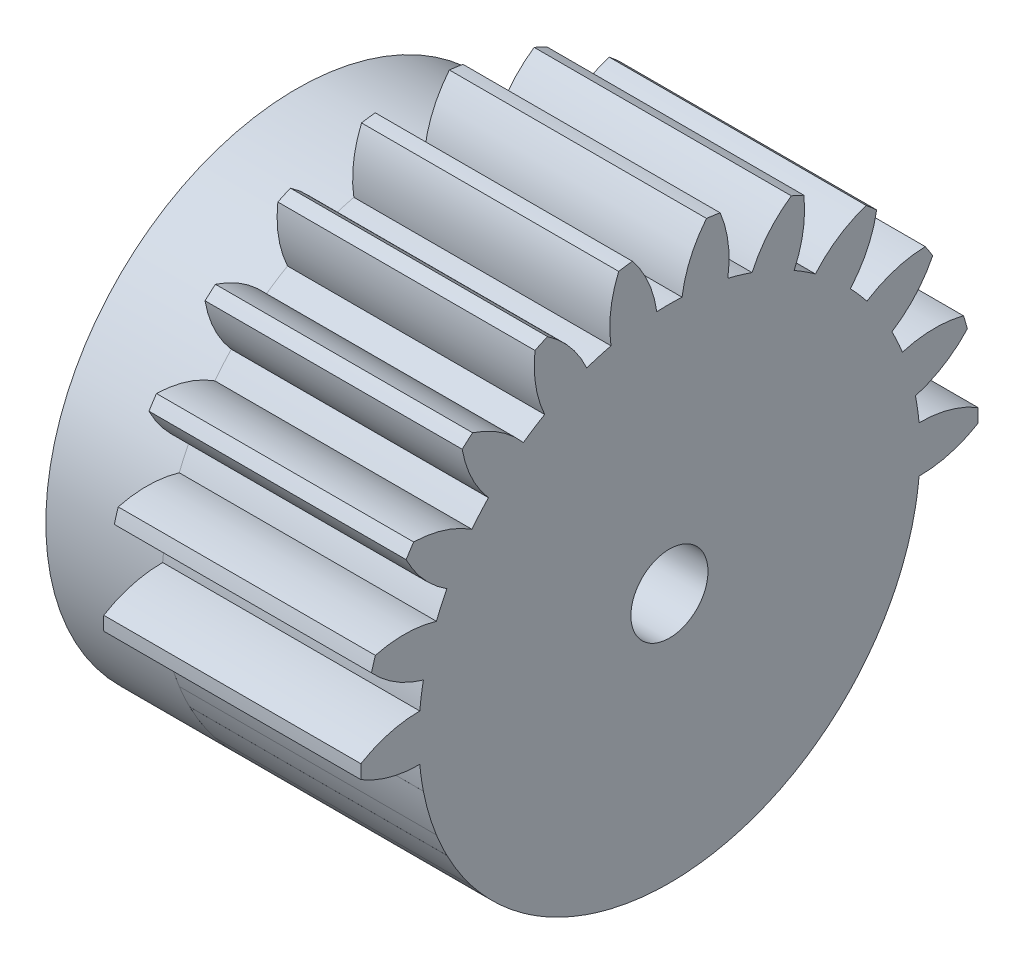
SolidWorks part; units mm, degrees
ref_plane "Front Plane" through (0, 0, 0) normal (0, 0, 1) x (1, 0, 0)
ref_plane "Top Plane" through (0, 0, 0) normal (0, 1, 0) x (1, 0, 0)
ref_plane "Right Plane" through (0, 0, 0) normal (1, 0, 0) x (0, 0, -1)
ref_plane "Plane2" through (4.0389, 0, 0) normal (1, 0, 0) x (0, 0, -1)
sketch "Sketch5" plane through (4.0389, 0, 0) normal (1, 0, 0) x (0, 0, -1)
  circle A0 centre (3.23, 4.4522) radius 1.5
  arc A1 (-8.767, 4.1839) -> (-6.4774, 3.5525) centre (-6.496, 7.9525) ccw
  arc A2 (-6.4774, 3.5525) -> (-6.3377, 2.5805) centre (3.23, 4.4522) ccw
  arc A3 (-6.3377, 2.5805) -> (-8.3567, 1.3296) centre (-5.1159, -1.6464) ccw
  arc A4 (-8.3567, 1.3296) -> (-8.2055, 0.8148) centre (3.23, 4.4522) ccw
  arc A5 (-8.2055, 0.8148) -> (-5.8308, 0.8541) centre (-7.0882, 5.0706) ccw
  arc A6 (-5.8308, 0.8541) -> (-5.4228, -0.0392) centre (3.23, 4.4522) ccw
  arc A7 (-5.4228, -0.0392) -> (-7.0076, -1.8082) centre (-3.0596, -3.7507) ccw
  arc A8 (-7.0076, -1.8082) -> (-6.7175, -2.2596) centre (3.23, 4.4522) ccw
  arc A9 (-6.7175, -2.2596) -> (-4.45, -1.5529) centre (-6.8444, 2.1386) ccw
  arc A10 (-4.45, -1.5529) -> (-3.807, -2.295) centre (3.23, 4.4522) ccw
  arc A11 (-3.807, -2.295) -> (-4.8292, -4.4389) centre (-0.4938, -5.1904) ccw
  arc A12 (-4.8292, -4.4389) -> (-4.4237, -4.7902) centre (3.23, 4.4522) ccw
  arc A13 (-4.4237, -4.7902) -> (-2.4471, -3.4733) centre (-5.7845, -0.606) ccw
  arc A14 (-2.4471, -3.4733) -> (-1.621, -4.0043) centre (3.23, 4.4522) ccw
  arc A15 (-1.621, -4.0043) -> (-1.9978, -6.3492) centre (2.3736, -5.8489) ccw
  arc A16 (-1.9978, -6.3492) -> (-1.5097, -6.5721) centre (3.23, 4.4522) ccw
  arc A17 (-1.5097, -6.5721) -> (0.0157, -4.7517) centre (-3.9943, -2.9408) ccw
  arc A18 (0.0157, -4.7517) -> (0.9579, -5.0284) centre (3.23, 4.4522) ccw
  arc A19 (0.9579, -5.0284) -> (1.257, -7.3845) centre (5.3105, -5.6729) ccw
  arc A20 (1.257, -7.3845) -> (1.7882, -7.4609) centre (3.23, 4.4522) ccw
  arc A21 (1.7882, -7.4609) -> (2.739, -5.2845) centre (-1.6189, -4.6766) ccw
  arc A22 (2.739, -5.2845) -> (3.721, -5.2845) centre (3.23, 4.4522) ccw
  arc A23 (3.721, -5.2845) -> (4.6718, -7.4609) centre (8.0788, -4.6766) ccw
  arc A24 (4.6718, -7.4609) -> (5.2029, -7.3845) centre (3.23, 4.4522) ccw
  arc A25 (5.2029, -7.3845) -> (5.502, -5.0284) centre (1.1494, -5.6729) ccw
  arc A26 (5.502, -5.0284) -> (6.4442, -4.7517) centre (3.23, 4.4522) ccw
  arc A27 (6.4442, -4.7517) -> (7.9696, -6.5721) centre (10.4542, -2.9408) ccw
  arc A28 (7.9696, -6.5721) -> (8.4577, -6.3492) centre (3.23, 4.4522) ccw
  arc A29 (8.4577, -6.3492) -> (8.0809, -4.0043) centre (4.0863, -5.8489) ccw
  arc A30 (8.0809, -4.0043) -> (8.907, -3.4733) centre (3.23, 4.4522) ccw
  arc A31 (8.907, -3.4733) -> (10.8836, -4.7902) centre (12.2444, -0.606) ccw
  arc A32 (10.8836, -4.7902) -> (11.2891, -4.4389) centre (3.23, 4.4522) ccw
  arc A33 (11.2891, -4.4389) -> (10.2669, -2.295) centre (6.9537, -5.1904) ccw
  arc A34 (10.2669, -2.295) -> (10.9099, -1.5529) centre (3.23, 4.4522) ccw
  arc A35 (10.9099, -1.5529) -> (13.1774, -2.2596) centre (13.3043, 2.1386) ccw
  arc A36 (13.1774, -2.2596) -> (13.4675, -1.8082) centre (3.23, 4.4522) ccw
  arc A37 (13.4675, -1.8082) -> (11.8827, -0.0392) centre (9.5195, -3.7507) ccw
  arc A38 (11.8827, -0.0392) -> (12.2907, 0.8541) centre (3.23, 4.4522) ccw
  arc A39 (12.2907, 0.8541) -> (14.6654, 0.8148) centre (13.5481, 5.0706) ccw
  arc A40 (14.6654, 0.8148) -> (14.8166, 1.3296) centre (3.23, 4.4522) ccw
  arc A41 (14.8166, 1.3296) -> (12.7976, 2.5805) centre (11.5758, -1.6464) ccw
  arc A42 (12.7976, 2.5805) -> (12.9374, 3.5525) centre (3.23, 4.4522) ccw
  arc A43 (12.9374, 3.5525) -> (15.227, 4.1839) centre (12.9559, 7.9525) ccw
  arc A44 (15.227, 4.1839) -> (15.227, 4.7205) centre (3.23, 4.4522) ccw
  arc A45 (15.227, 4.7205) -> (12.9374, 5.3518) centre (12.9559, 0.9519) ccw
  arc A46 (12.9374, 5.3518) -> (12.7976, 6.3238) centre (3.23, 4.4522) ccw
  arc A47 (12.7976, 6.3238) -> (14.8166, 7.5747) centre (11.5758, 10.5508) ccw
  arc A48 (14.8166, 7.5747) -> (14.6654, 8.0895) centre (3.23, 4.4522) ccw
  arc A49 (14.6654, 8.0895) -> (12.2907, 8.0503) centre (13.5481, 3.8338) ccw
  arc A50 (12.2907, 8.0503) -> (11.8827, 8.9435) centre (3.23, 4.4522) ccw
  arc A51 (11.8827, 8.9435) -> (13.4675, 10.7125) centre (9.5195, 12.655) ccw
  arc A52 (13.4675, 10.7125) -> (13.1774, 11.1639) centre (3.23, 4.4522) ccw
  arc A53 (13.1774, 11.1639) -> (10.9099, 10.4572) centre (13.3043, 6.7658) ccw
  arc A54 (10.9099, 10.4572) -> (10.2669, 11.1994) centre (3.23, 4.4522) ccw
  arc A55 (10.2669, 11.1994) -> (11.2891, 13.3432) centre (6.9537, 14.0947) ccw
  arc A56 (11.2891, 13.3432) -> (10.8836, 13.6946) centre (3.23, 4.4522) ccw
  arc A57 (10.8836, 13.6946) -> (8.907, 12.3777) centre (12.2444, 9.5103) ccw
  arc A58 (8.907, 12.3777) -> (8.0809, 12.9086) centre (3.23, 4.4522) ccw
  arc A59 (8.0809, 12.9086) -> (8.4577, 15.2536) centre (4.0863, 14.7533) ccw
  arc A60 (8.4577, 15.2536) -> (7.9696, 15.4765) centre (3.23, 4.4522) ccw
  arc A61 (7.9696, 15.4765) -> (6.4442, 13.6561) centre (10.4542, 11.8451) ccw
  arc A62 (6.4442, 13.6561) -> (5.502, 13.9327) centre (3.23, 4.4522) ccw
  arc A63 (5.502, 13.9327) -> (5.2029, 16.2889) centre (1.1494, 14.5772) ccw
  arc A64 (5.2029, 16.2889) -> (4.6718, 16.3652) centre (3.23, 4.4522) ccw
  arc A65 (4.6718, 16.3652) -> (3.721, 14.1888) centre (8.0788, 13.581) ccw
  arc A66 (3.721, 14.1888) -> (2.739, 14.1888) centre (3.23, 4.4522) ccw
  arc A67 (2.739, 14.1888) -> (1.7882, 16.3652) centre (-1.6189, 13.581) ccw
  arc A68 (1.7882, 16.3652) -> (1.257, 16.2889) centre (3.23, 4.4522) ccw
  arc A69 (1.257, 16.2889) -> (0.9579, 13.9327) centre (5.3105, 14.5772) ccw
  arc A70 (0.9579, 13.9327) -> (0.0157, 13.6561) centre (3.23, 4.4522) ccw
  arc A71 (0.0157, 13.6561) -> (-1.5097, 15.4765) centre (-3.9943, 11.8451) ccw
  arc A72 (-1.5097, 15.4765) -> (-1.9978, 15.2536) centre (3.23, 4.4522) ccw
  arc A73 (-1.9978, 15.2536) -> (-1.621, 12.9086) centre (2.3736, 14.7533) ccw
  arc A74 (-1.621, 12.9086) -> (-2.4471, 12.3777) centre (3.23, 4.4522) ccw
  arc A75 (-2.4471, 12.3777) -> (-4.4237, 13.6946) centre (-5.7845, 9.5103) ccw
  arc A76 (-4.4237, 13.6946) -> (-4.8292, 13.3432) centre (3.23, 4.4522) ccw
  arc A77 (-4.8292, 13.3432) -> (-3.807, 11.1994) centre (-0.4938, 14.0947) ccw
  arc A78 (-3.807, 11.1994) -> (-4.45, 10.4572) centre (3.23, 4.4522) ccw
  arc A79 (-4.45, 10.4572) -> (-6.7175, 11.1639) centre (-6.8444, 6.7658) ccw
  arc A80 (-6.7175, 11.1639) -> (-7.0076, 10.7125) centre (3.23, 4.4522) ccw
  arc A81 (-7.0076, 10.7125) -> (-5.4228, 8.9435) centre (-3.0596, 12.655) ccw
  arc A82 (-5.4228, 8.9435) -> (-5.8308, 8.0503) centre (3.23, 4.4522) ccw
  arc A83 (-5.8308, 8.0503) -> (-8.2055, 8.0895) centre (-7.0882, 3.8338) ccw
  arc A84 (-8.2055, 8.0895) -> (-8.3567, 7.5747) centre (3.23, 4.4522) ccw
  arc A85 (-8.3567, 7.5747) -> (-6.3377, 6.3238) centre (-5.1159, 10.5508) ccw
  arc A86 (-6.3377, 6.3238) -> (-6.4774, 5.3518) centre (3.23, 4.4522) ccw
  arc A87 (-6.4774, 5.3518) -> (-8.767, 4.7205) centre (-6.496, 0.9519) ccw
  arc A88 (-8.767, 4.7205) -> (-8.767, 4.1839) centre (3.23, 4.4522) ccw
extrude "Boss-Extrude1" add sketch "Sketch5" against normal blind 10 separate body
ref_plane "Plane3" through (0, 0, -3.23) normal (0, 0, 1) x (1, 0, 0)
sketch "Sketch10" plane through (0, 0, -3.23) normal (0, 0, 1) x (1, 0, 0)
  line L0 (-5.9611, 7.9022) -> (-5.9611, 14.2022)
  line L1 (-5.9611, 14.2022) -> (-10.4611, 14.2022)
  line L2 (-10.4611, 14.2022) -> (-10.4611, 7.9022)
  line L3 (-10.4611, 7.9022) -> (-5.9611, 7.9022)
  line L4 (-10.4611, 4.4522) -> (-5.9611, 4.4522) construction
revolve "Revolve2" add sketch "Sketch10" angle 360 about L4 reverse direction yes
sketch "Sketch11" plane through (4.0389, 0, 0) normal (1, 0, 0) x (0, 0, -1)
  line L1 (-9.2027, 3.156) -> (-6.4335, 3.156)
  line L2 (12.8934, 3.156) -> (15.6626, 3.156)
  arc A0 (-6.4335, 3.156) -> (12.8934, 3.156) centre (3.23, 4.4522) ccw
  arc A1 (-9.2027, 3.156) -> (15.6626, 3.156) centre (3.23, 4.4522) ccw
  dimension "D1" = 19.5
  dimension "D2" = 25
extrude "Cut-Extrude1" cut sketch "Sketch11" against normal blind 10
